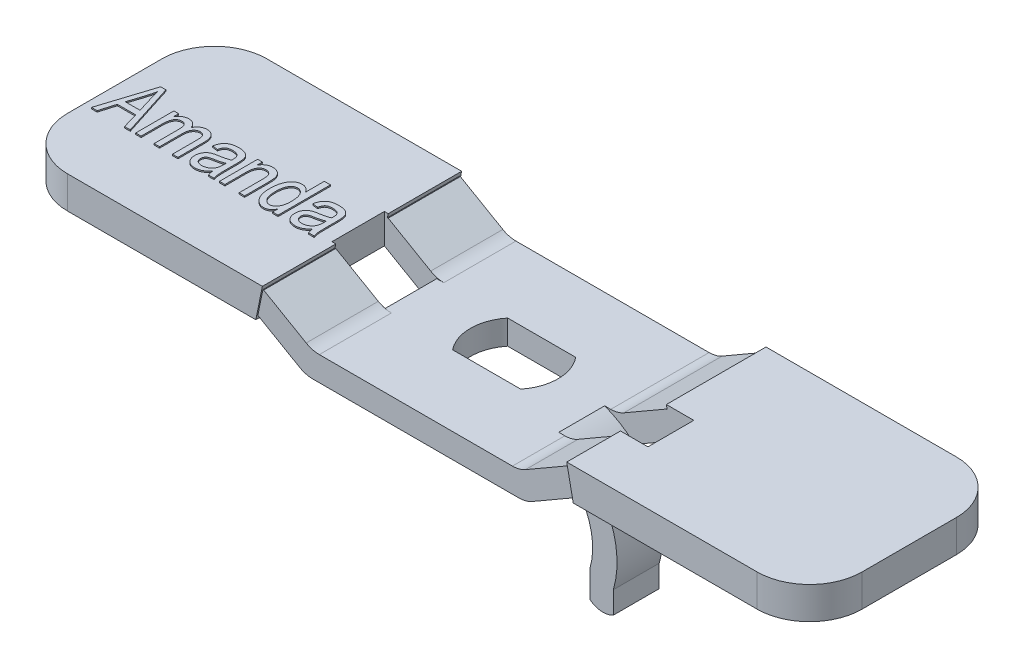
SolidWorks part; units mm, degrees
material "AISI 304"
ref_plane "Front Plane" through (0, 0, 0) normal (0, 0, 1) x (1, 0, 0)
ref_plane "Top Plane" through (0, 0, 0) normal (0, 1, 0) x (1, 0, 0)
ref_plane "Right Plane" through (0, 0, 0) normal (1, 0, 0) x (0, 0, -1)
sketch "Sketch1" plane through (0, 0, 0) normal (0, 0, 1) x (1, 0, 0)
  line L3 (-38.3113, 5.08) -> (-14.7424, 5.08)
  line L8 (-15.3754, 2.7178) -> (-38.3113, 2.7178)
  line L9 (-38.3113, 2.7178) -> (-38.3113, 5.08)
  line L10 (-10.668, 0) -> (-15.3754, 2.7178)
  line L11 (10.668, 0) -> (15.3754, 2.7178)
  line L12 (10.0351, 2.3622) -> (14.7424, 5.08)
  line L13 (-10.668, 0) -> (10.668, 0)
  line L14 (-10.0351, 2.3622) -> (10.0351, 2.3622)
  line L15 (15.3754, 2.7178) -> (37.8887, 2.7178)
  line L16 (-10.0351, 2.3622) -> (-14.7424, 5.08)
  line L17 (14.7424, 5.08) -> (37.8887, 5.08)
  line L18 (-10.0351, 2.3622) -> (10.0351, 2.3622)
  line L19 (37.8887, 2.7178) -> (37.8887, 5.08)
  line L20 (10.668, 0) -> (19.4668, 5.08) construction
  line L25 (-10.668, 0) -> (-19.4668, 5.08) construction
  line L26 (-10.0351, 2.3622) -> (-18.2857, 7.1257) construction
  line L27 (10.0351, 2.3622) -> (18.2857, 7.1257) construction
  point P4 (0, 0)
  point P5 (-35.9491, 2.3622)
  point P7 (35.5265, 2.3622)
  point P8 (35.5265, 2.7178)
  point P9 (-35.9491, 2.7178)
  dimension "D1" = 76.2
  dimension "D2" = 5.08
  dimension "D3" = 2.3622
  dimension "D4" = 2.3622
  dimension "D5" = 22.5134
  dimension "D6" = 21.336
  dimension "D7" = 30
  dimension "D8" = 30
  dimension "D9" = 2.3622
extrude "Boss-Extrude1" add sketch "Sketch1" along normal mid plane 19.05 contours L15 L19 L17 L12 L14 L16 L3 L9 L8 L10 L13 L11 region at (-26.5268, 4.3163, 0)
fillet "Fillet1" radius 5.08 4 edges at (37.8887, 3.8989, -9.525) (37.8887, 3.8989, 9.525) (-38.3113, 3.8989, 9.525) (-38.3113, 3.8989, -9.525)
sketch "Sketch3" plane through (0, 0, 0) normal (0, 0, 1) x (1, 0, 0)
  line L4 (-38.3113, 5.461) -> (-33.2313, 5.461)
  line L5 (-33.2313, 5.461) -> (-14.7424, 5.461)
  line L7 (-38.6923, 5.461) -> (-14.7424, 5.461)
  line L10 (15.3754, 2.3368) -> (32.8087, 2.3368)
  line L11 (-33.2313, 2.3368) -> (-38.3113, 2.3368)
  line L12 (-15.3754, 2.3368) -> (-33.2313, 2.3368)
  line L13 (15.3754, 2.3368) -> (38.2697, 2.3368)
  line L14 (-15.3754, 2.3368) -> (-38.6923, 2.3368)
  line L18 (38.2697, 5.461) -> (38.2697, 2.3368)
  line L19 (14.7424, 5.461) -> (32.8087, 5.461)
  line L20 (14.7424, 5.461) -> (38.2697, 5.461)
  line L21 (-38.6923, 5.461) -> (-38.6923, 2.3368)
  line L22 (-38.3113, 2.7178) -> (-38.3113, 5.08) construction
  line L23 (37.8887, 5.08) -> (37.8887, 2.7178) construction
  line L24 (-14.7424, 5.461) -> (-15.3754, 2.3368)
  line L25 (14.7424, 5.461) -> (15.3754, 2.3368)
  dimension "D5" = 0.381
  dimension "D6" = 0.381
  dimension "D1" = 0.381
  dimension "D2" = 0.381
  dimension "D3" = 0.381
  dimension "D4" = 0.381
extrude "Boss-Extrude2" add sketch "Sketch3" along normal mid plane 19.304
sketch "Sketch2" plane through (0, 0, 0) normal (0, 1, 0) x (1, 0, 0)
  line L0 (-10.0351, -9.525) -> (-10.0351, 9.525) construction
  line L1 (-10.0351, 2.54) -> (-15.1151, 2.54)
  line L2 (-10.0351, 2.54) -> (-10.0351, -2.54)
  line L3 (-10.0351, -2.54) -> (-15.1151, -2.54)
  line L4 (-15.1151, 2.54) -> (-15.1151, -2.54)
  line L5 (0, 0) -> (26.5905, 0) construction
  line L6 (10.0351, -9.525) -> (10.0351, 9.525) construction
  line L7 (8.7651, 0) -> (17.4011, 0)
  line L8 (8.7651, 0) -> (8.7651, -4.445)
  line L9 (8.7651, -4.445) -> (17.4011, -4.445)
  line L10 (17.4011, 0) -> (17.4011, -4.445)
  line L12 (3.2985, -2.667) -> (-3.2985, -2.667)
  line L14 (3.2985, 2.667) -> (-3.2985, 2.667)
  line L16 (0, 2.667) -> (0, -2.667) construction
  line L17 (3.302, 0) -> (-3.302, 0) construction
  arc A0 (-3.2985, 2.667) -> (-3.2985, -2.667) centre (0, 0) ccw
  arc A1 (3.2985, -2.667) -> (3.2985, 2.667) centre (0, 0) ccw
  point P6 (-10.0351, 0)
  dimension "D8" = 8.4836
  dimension "D1" = 5.08
  dimension "D2" = 5.08
  dimension "D3" = 8.636
  dimension "D4" = 1.27
  dimension "D5" = 4.445
  dimension "D6" = 5.334
  dimension "D7" = 6.597
extrude "Cut-Extrude1" cut sketch "Sketch2" along normal blind 19.05
fillet "Fillet2" radius 5.08 4 edges at (38.2697, 3.8989, -9.652) (38.2697, 3.8989, 9.652) (-38.6923, 3.8989, -9.652) (-38.6923, 3.8989, 9.652)
sketch "Sketch4" plane through (0, 0, 0) normal (0, 0, 1) x (1, 0, 0)
  line L0 (8.7651, 2.3622) -> (8.7651, 0)
  line L1 (11.7741, -7.576) -> (11.7741, -10.1611)
  line L3 (14.0511, -10.3378) -> (14.0511, -8.2047)
  line L4 (8.7651, 2.3622) -> (8.7651, 0) construction
  arc A0 (8.7651, 2.3622) -> (14.0511, -8.2047) centre (5.7675, -5.7429) cw
  arc A1 (8.7651, 0) -> (11.7741, -7.576) centre (5.4704, -5.6941) cw
  arc A2 (11.7741, -10.1611) -> (14.0511, -10.3378) centre (13.0492, -8.4897) ccw
  dimension "D1" = 2.3622
  dimension "D2" = 6.5786
  dimension "D3" = 12.7
  dimension "D4" = 8.6417
  dimension "D5" = 2.1022
  dimension "D6" = 3.0091
  dimension "D7" = 4.2842
  dimension "D8" = 5.2861
  dimension "D9" = 2.9976
extrude "Boss-Extrude3" add sketch "Sketch4" along normal up to surface (4.445 mm away) up to face at (13.4565, 3.0144, 4.445)
fillet "Fillet3" radius 2.54 7 edges at (10.668, 0, 6.985) (10.668, 0, -4.7625) (-10.668, 0, 6.0325) (-10.0351, 2.3622, -6.0325) (10.0351, 2.3622, 6.985) (10.0351, 2.3622, -4.7625) (-10.0351, 2.3622, 6.0325)
sketch "Sketch5" plane through (0, 5.461, 0) normal (0, 1, 0) x (1, 0, 0)
  line L129 (-37.9052, -3.048) -> (-16.7109, -3.048) construction
  text T0 "Amanda" font "Arial Narrow" height 5.08
  dimension "D1" = 2
extrude "Boss-Extrude4" add sketch "Sketch5" along normal blind 0.127
